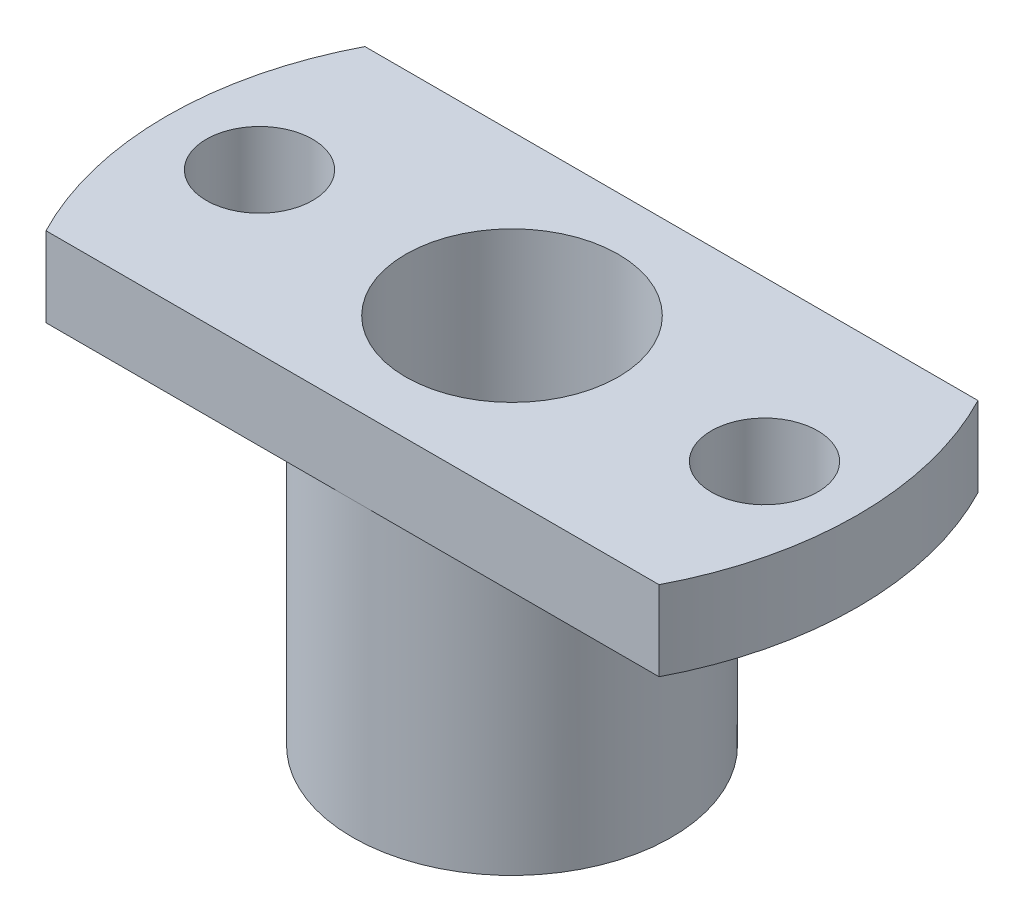
SolidWorks part; units mm, degrees
ref_plane "Front Plane" through (0, 0, 0) normal (0, 0, 1) x (1, 0, 0)
ref_plane "Top Plane" through (0, 0, 0) normal (0, 1, 0) x (1, 0, 0)
ref_plane "Right Plane" through (0, 0, 0) normal (1, 0, 0) x (0, 0, -1)
sketch "Sketch1" plane through (0, 0, 0) normal (0, 1, 0) x (1, 0, 0)
  circle A0 centre (0, 0) radius 3
  circle A1 centre (0, 0) radius 2
extrude "Boss-Extrude1" add sketch "Sketch1" along normal blind 5.5
sketch "Sketch2" plane through (0, 5.5, 0) normal (0, 1, 0) x (1, 0, 0)
  line L1 (5.7663, 3) -> (-5.7663, 3)
  line L2 (5.7663, -3) -> (-5.7663, -3)
  arc A1 (5.7663, -3) -> (5.7663, 3) centre (0, 0) ccw
  arc A2 (-5.7663, 3) -> (-5.7663, -3) centre (0, 0) ccw
  point P0 (6, 3)
  point P4 (0, 0)
  point P6 (-6, 3)
  point P7 (6, -3)
  point P8 (-6, -3)
extrude "Boss-Extrude2" add sketch "Sketch2" along normal blind 1.5
sketch "Sketch3" plane through (0, 5.5, 0) normal (0, -1, 0) x (1, 0, 0)
  circle A0 centre (0, 0) radius 2
extrude "Cut-Extrude1" cut sketch "Sketch3" against normal blind 11.5
sketch "Sketch4" plane through (0, 7, 0) normal (0, 1, 0) x (1, 0, 0)
  line L0 (4.75, 0) -> (-4.75, 0)
  circle A0 centre (-4.75, 0) radius 1
  circle A1 centre (4.75, 0) radius 1
  point P4 (0, 0)
  dimension "D1" = 9.5
extrude "Cut-Extrude2" cut sketch "Sketch4" against normal blind 11.5 contours A0 | A1 region at (-5.7217, 7, 0) region at (4.75, 7, -0.9717)
chamfer "Chamfer1" distance 1 angle 45 1 edges at (0, 0, 2)
